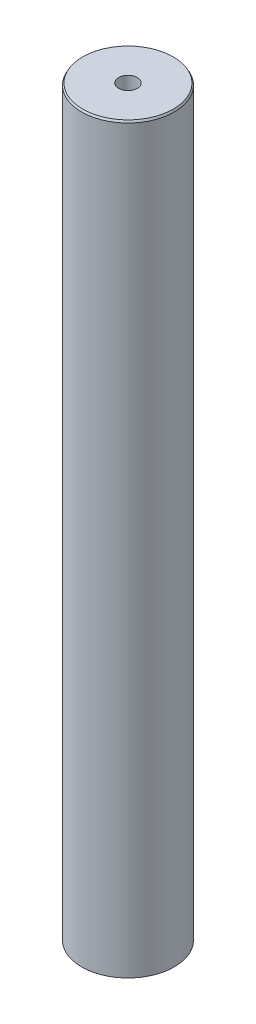
SolidWorks part; units mm, degrees
ref_plane "Front Plane" through (0, 0, 0) normal (0, 0, 1) x (1, 0, 0)
ref_plane "Top Plane" through (0, 0, 0) normal (0, 1, 0) x (1, 0, 0)
ref_plane "Right Plane" through (0, 0, 0) normal (1, 0, 0) x (0, 0, -1)
sketch "Sketch1" plane through (0, 0, 0) normal (0, 1, 0) x (1, 0, 0)
  circle A0 centre (0, 0) radius 5
  dimension "SHAFT_OD" = 10
extrude "Boss-Extrude1" add sketch "Sketch1" along normal blind 80.1439
sketch "Sketch2" plane through (0, 0, 0) normal (0, 1, 0) x (1, 0, 0)
  circle A0 centre (0, 0) radius 1.0099
  dimension "BORE_D" = 2.0198
extrude "Cut-Extrude1" cut sketch "Sketch2" along normal through all
chamfer "Chamfer1" distance 0.2072 angle 30 2 edges at (0, 80.1439, 5) (0, 0, 5) first distance on face at (0, 80.1439, 5) first distance on face at (0, 0, 1.0099)
